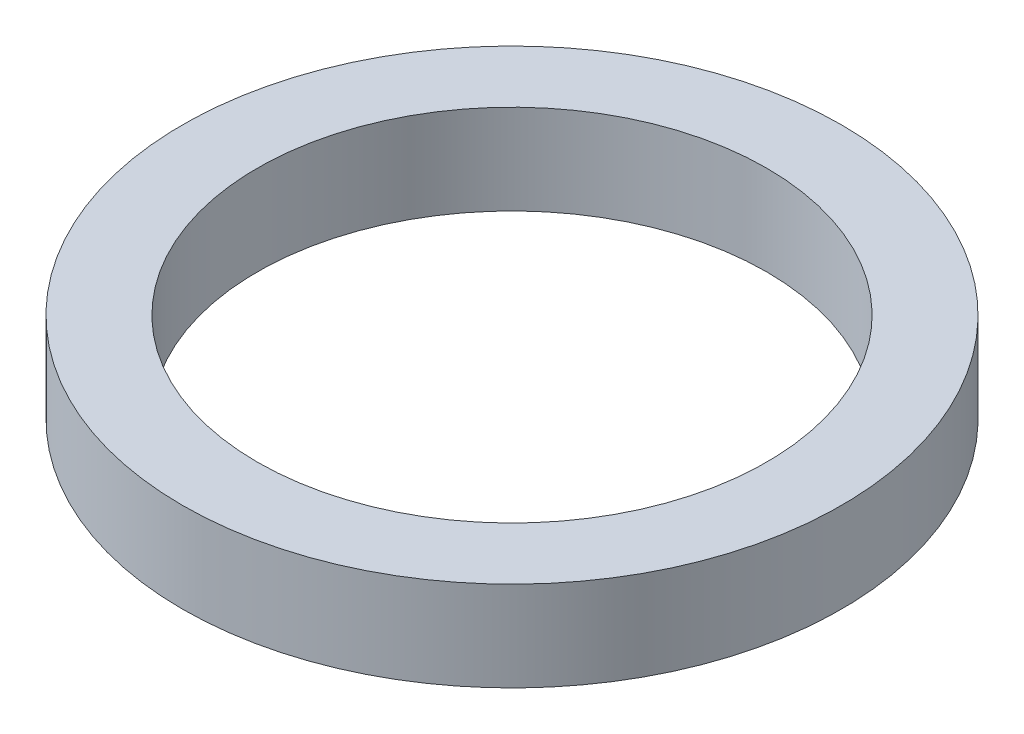
SolidWorks part; units mm, degrees
ref_plane "Front Plane" through (0, 0, 0) normal (0, 0, 1) x (1, 0, 0)
ref_plane "Top Plane" through (0, 0, 0) normal (0, 1, 0) x (1, 0, 0)
ref_plane "Right Plane" through (0, 0, 0) normal (1, 0, 0) x (0, 0, -1)
sketch "Sketch1" plane through (0, 0, 0) normal (0, 1, 0) x (1, 0, 0)
  circle A0 centre (0, 0) radius 55
  dimension "FLANGE_OD" = 110
extrude "Boss-Extrude1" add sketch "Sketch1" along normal blind 15
sketch "Sketch2" plane through (0, 0, 0) normal (0, 1, 0) x (1, 0, 0)
  circle A0 centre (0, 0) radius 42.5
  dimension "BORE_D" = 85
extrude "Cut-Extrude1" cut sketch "Sketch2" along normal through all
sketch "Sketch3" plane through (0, 15, 0) normal (0, 1, 0) x (1, 0, 0)
  circle A0 centre (0, 0) radius 25.4198 construction
  circle A1 centre (-25.4198, 0) radius 1.7432
  dimension "BOLT_D" = 3.4864
  dimension "BOLT_PCD" = 50.8397
extrude "Cut-Extrude2" cut sketch "Sketch3" against normal blind 9.3248 rebuild error yes
pattern_circular "CirPattern1" count 5 over 360 rebuild error yes
